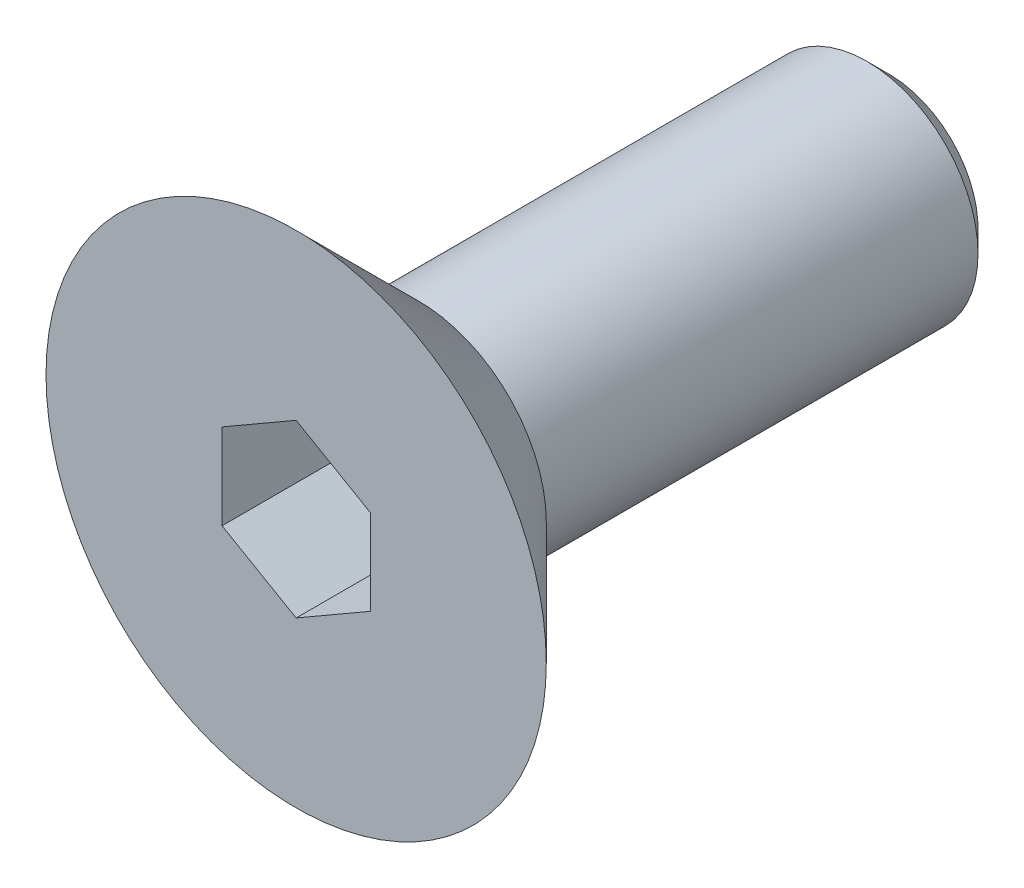
SolidWorks part; units mm, degrees
ref_plane "Front Plane" through (0, 0, 0) normal (0, 0, 1) x (1, 0, 0)
ref_plane "Top Plane" through (0, 0, 0) normal (0, 1, 0) x (1, 0, 0)
ref_plane "Right Plane" through (0, 0, 0) normal (1, 0, 0) x (0, 0, -1)
sketch "Sketch1" plane through (0, 0, 0) normal (0, 0, 1) x (1, 0, 0)
  circle A0 centre (0, 0) radius 3.375
  dimension "D1" = 6.75
extrude "Boss-Extrude1" add sketch "Sketch1" along normal blind 1.65
sketch "Sketch2" plane through (0, 0, 0) normal (0, 0, -1) x (-1, 0, 0)
  circle A0 centre (0, 0) radius 1.5
  dimension "D1" = 3
extrude "Boss-Extrude2" add sketch "Sketch2" along normal blind 6.35
chamfer "Chamfer1" distance 0.3 angle 45 1 edges at (-1.5, 0, -6.35)
sketch "Sketch3" plane through (0, 0, 1.65) normal (0, 0, 1) x (1, 0, 0)
  line L1 (0, 1.1547) -> (-1, 0.5774)
  line L2 (-1, 0.5774) -> (-1, -0.5774)
  line L3 (-1, -0.5774) -> (0, -1.1547)
  line L4 (0, -1.1547) -> (1, -0.5774)
  line L5 (1, -0.5774) -> (1, 0.5774)
  line L6 (1, 0.5774) -> (0, 1.1547)
  circle A0 centre (0, 0) radius 1 construction
  dimension "D1" = 2
extrude "Cut-Extrude1" cut sketch "Sketch3" against normal blind 2
chamfer "Chamfer2" distance 1.65 angle 45 1 edges at (3.375, 0, 0)
